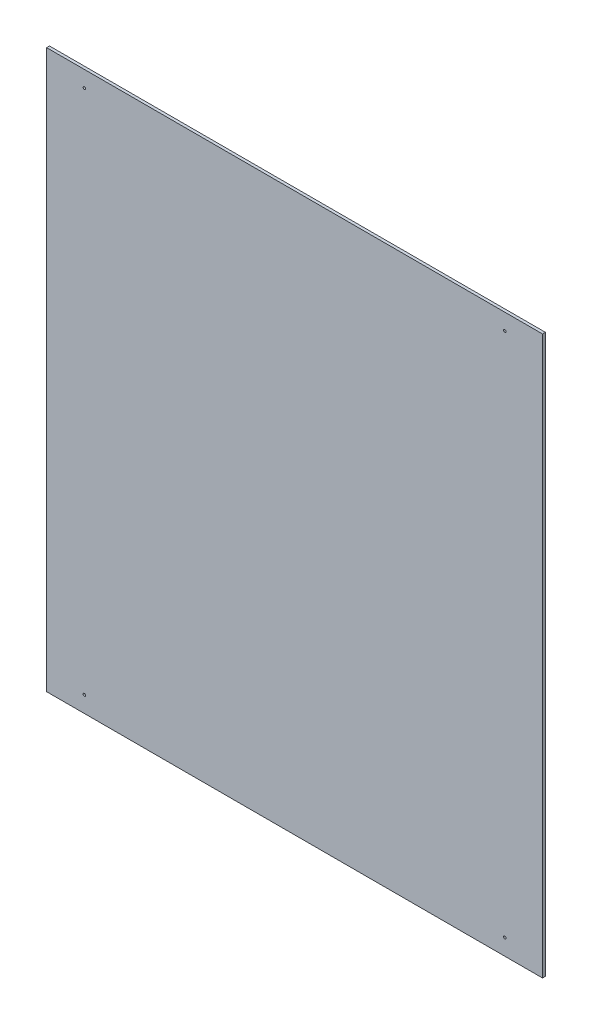
SolidWorks part; units mm, degrees
ref_plane "Front Plane" through (0, 0, 0) normal (0, 0, 1) x (1, 0, 0)
ref_plane "Top Plane" through (0, 0, 0) normal (0, 1, 0) x (1, 0, 0)
ref_plane "Right Plane" through (0, 0, 0) normal (1, 0, 0) x (0, 0, -1)
sketch "Sketch1" plane through (0, 0, 0) normal (0, 0, 1) x (1, 0, 0)
  line L1 (200, -225) -> (-200, -225)
  line L2 (200, -225) -> (200, 225)
  line L3 (200, 225) -> (-200, 225)
  line L4 (-200, -225) -> (-200, 225)
  line L5 (200, -225) -> (-200, 225) construction
  line L6 (200, 225) -> (-200, -225) construction
  point P0 (0, 0)
  dimension "D1" = 450
  dimension "D2" = 400
base flange "Base-Flange1" sketch "Sketch1" thickness 2.3 reverse thickness direction no parameters "D1"=1.6
sketch "Sketch5" plane through (0, 0, 0) normal (0, 0, 1) x (1, 0, 0)
  line L0 (200, 225) -> (-200, 225) construction
  line L1 (200, -225) -> (200, 225) construction
  circle A0 centre (169.61, 211.94) radius 1
  point P6 (0, 0)
  dimension "D1" = 2
  dimension "D2" = 13.06
  dimension "D3" = 30.39
extrude "Cut-Extrude4" cut sketch "Sketch5" against normal through all normal cut yes
mirror "Mirror3" about plane through (0, 0, 0) normal (0, 1, 0) of "Cut-Extrude4"
mirror "Mirror4" about plane through (0, 0, 0) normal (1, 0, 0) of "Mirror3", "Cut-Extrude4"
sketch "Bend-Lines1" [suppressed] plane through (0, 0, 0) normal (0, 1, 0) x (1, 0, 0)
sketch "Bounding-Box1" [suppressed] plane through (0, 0, 0) normal (0, 1, 0) x (1, 0, 0)
sheet metal parameters "Sheet-Metal1" thickness 2.3 parameters "D1"=1.6
flat pattern "Flat-Pattern1" [suppressed]
sketch "Bend-Lines2" plane through (0, 0, 0) normal (0, 1, 0) x (1, 0, 0)
sketch3d "Bounding-Box2" [suppressed]
  line L0 (200, 225, 0) -> (200, -225, 0) construction
  line L1 (-200, 225, 0) -> (-200, -225, 0) construction
  line L2 (200, 225, 0) -> (-200, 225, 0) construction
  line L3 (200, -225, 0) -> (-200, -225, 0) construction
sheet metal parameters "Sheet-Metal7" thickness 2.3 parameters "D1"=1.6
flat pattern "Flat-Pattern1"
sketch "Bend-Lines2" plane through (0, 0, 0) normal (0, 1, 0) x (1, 0, 0)
sketch3d "Bounding-Box2" [suppressed]
  line L0 (200, 225, 0) -> (200, -225, 0) construction
  line L1 (-200, 225, 0) -> (-200, -225, 0) construction
  line L2 (200, 225, 0) -> (-200, 225, 0) construction
  line L3 (200, -225, 0) -> (-200, -225, 0) construction
sheet metal parameters "Sheet-Metal8" thickness 2.3 parameters "D1"=1.6
flat pattern "Flat-Pattern1"
sketch "Bend-Lines2" plane through (0, 0, 0) normal (0, 1, 0) x (1, 0, 0)
sketch3d "Bounding-Box2" [suppressed]
  line L0 (200, 225, 0) -> (200, -225, 0) construction
  line L1 (-200, 225, 0) -> (-200, -225, 0) construction
  line L2 (200, 225, 0) -> (-200, 225, 0) construction
  line L3 (200, -225, 0) -> (-200, -225, 0) construction
sheet metal parameters "Sheet-Metal9" thickness 2.3 parameters "D1"=1.6
flat pattern "Flat-Pattern1"
sketch "Bend-Lines2" plane through (0, 0, 0) normal (0, 1, 0) x (1, 0, 0)
sketch3d "Bounding-Box2" [suppressed]
  line L0 (200, 225, 0) -> (200, -225, 0) construction
  line L1 (-200, 225, 0) -> (-200, -225, 0) construction
  line L2 (200, 225, 0) -> (-200, 225, 0) construction
  line L3 (200, -225, 0) -> (-200, -225, 0) construction
